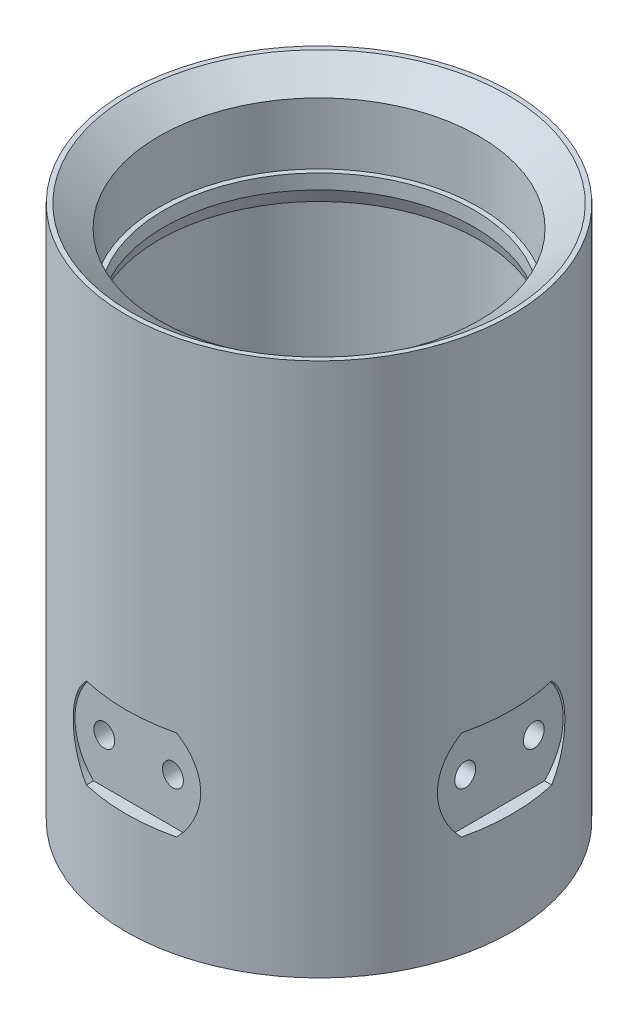
SolidWorks part; units mm, degrees
ref_plane "Front Plane" through (0, 0, 0) normal (0, 0, 1) x (1, 0, 0)
ref_plane "Top Plane" through (0, 0, 0) normal (0, 1, 0) x (1, 0, 0)
ref_plane "Right Plane" through (0, 0, 0) normal (1, 0, 0) x (0, 0, -1)
sketch "Sketch2" plane through (0, 0, 0) normal (0, 1, 0) x (1, 0, 0)
  circle A0 centre (0, 0) radius 39.35
  circle A1 centre (0, 0) radius 32.6
  dimension "D1" = 78.7
  dimension "D2" = 65.2
extrude "Boss-Extrude1" add sketch "Sketch2" along normal blind 109
sketch "Sketch3" plane through (0, 0, 0) normal (0, 0, 1) x (1, 0, 0)
  line L1 (9.1924, 39.1924) -> (-9.1924, 39.1924)
  line L3 (-9.1924, 20.8076) -> (9.1924, 20.8076)
  arc A0 (-9.1924, 39.1924) -> (-9.1924, 20.8076) centre (0, 30) ccw
  arc A1 (9.1924, 20.8076) -> (9.1924, 39.1924) centre (0, 30) ccw
  dimension "D1" = 26
  dimension "D2" = 30
extrude "Cut-Extrude1" cut sketch "Sketch3" against normal blind 2.5 and the other way through all from offset 39.3
ref_axis "Axis1" through (0, 109, 0) along (0, -1, 0)
sketch "Sketch4" plane through (0, 0, 36.8) normal (0, 0, 1) x (1, 0, 0)
  line L0 (-9.1924, 20.8076) -> (9.1924, 20.8076) construction
  ellipse E0 centre (-7, 30) end of major axis (-7, 32.3375) minor radius 2.125
  ellipse E1 centre (7, 30) end of major axis (7, 27.6625) minor radius 2.125
  point P15 (-7, 30)
  point P16 (7, 30)
  dimension "D1" = 9.1924
  dimension "D2" = 9.1924
  dimension "D3" = 14
extrude "Cut-Extrude2" cut sketch "Sketch4" against normal up to next
pattern_circular "CirPattern1" count 4 over 360 about axis through (0, 109, 0) along (0, -1, 0) of "Cut-Extrude1", "Cut-Extrude2"
chamfer "Chamfer1" distance 5.8 distance2 4.4 1 edges at (0, 109, 32.6) first distance on face at (0, 109, 39.35)
sketch "Sketch5" plane through (0, 0, 0) normal (0, -1, 0) x (-1, 0, 0)
  circle A0 centre (0, 0) radius 32.6
  circle A1 centre (0, 0) radius 31.6
  dimension "D1" = 65.2
  dimension "D2" = 63.2
extrude "Boss-Extrude2" add sketch "Sketch5" against normal blind 3
sketch "Sketch6" plane through (0, 0, 0) normal (0, -1, 0) x (1, 0, 0)
  circle A0 centre (0, 0) radius 31.6
  circle A1 centre (0, 0) radius 32.6
  dimension "D1" = 65.2
  dimension "D2" = 63.2
extrude "Boss-Extrude3" add sketch "Sketch6" along normal blind 6 from offset 92.05 offset against normal yes
chamfer "Chamfer2" distance 3 angle 20 1 edges at (0, 86.05, -31.6) first distance on face at (0, 86.05, -31.6)
sketch "Sketch7" plane through (0, 0, 0) normal (0, -1, 0) x (1, 0, 0)
  circle A0 centre (0, 0) radius 32.6
  circle A1 centre (0, 0) radius 31.6
  dimension "D1" = 65.2
  dimension "D2" = 63.2
extrude "Boss-Extrude4" add sketch "Sketch7" against normal blind 3 from offset 10.2 separate body offset against normal yes
